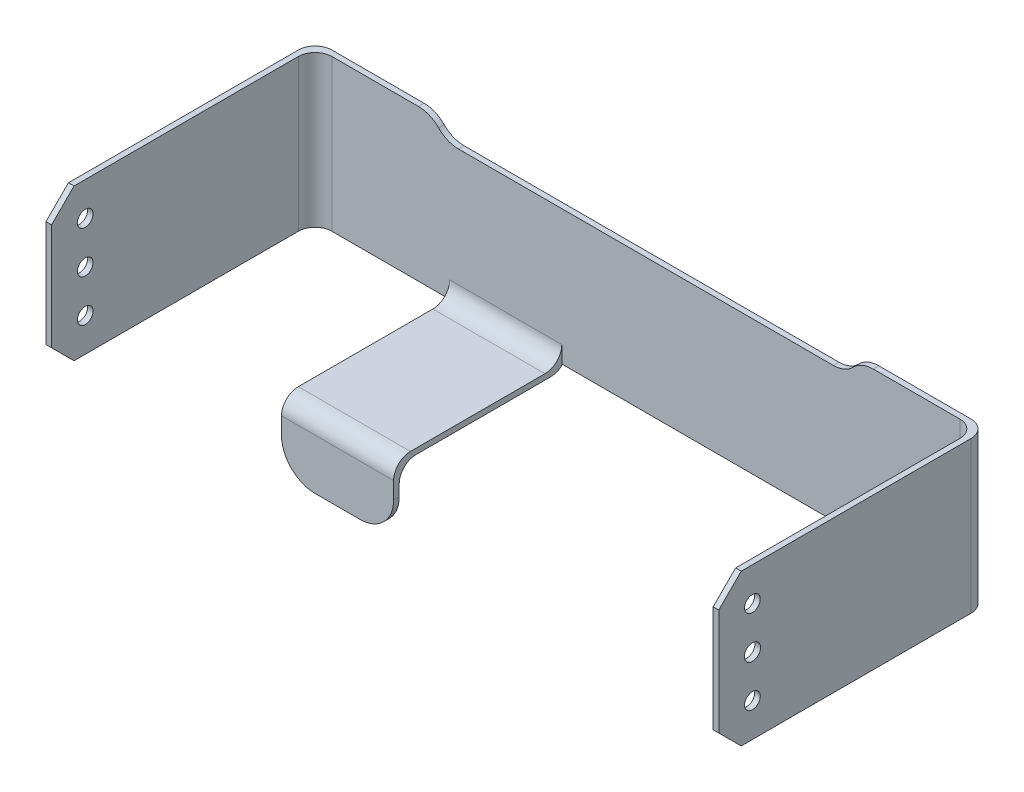
SolidWorks part; units mm, degrees
ref_plane "Front Plane" through (0, 0, 0) normal (0, 0, 1) x (1, 0, 0)
ref_plane "Top Plane" through (0, 0, 0) normal (0, 1, 0) x (1, 0, 0)
ref_plane "Right Plane" through (0, 0, 0) normal (1, 0, 0) x (0, 0, -1)
sketch "Sketch1" plane through (0, 0, 0) normal (0, 0, 1) x (1, 0, 0)
  line L0 (-1120, 0) -> (-60, 0) construction
  line L1 (0, -1000) -> (0, -10.5) construction
  line L9 (60, 0) -> (27292.9876, 0) construction
  line L10 (-38, -13.5) -> (38, -13.5)
  line L11 (-60, -13.5) -> (-60, 13.5)
  line L12 (-60, 13.5) -> (-38, 13.5)
  line L13 (-38, 13.5) -> (-38, 10.5)
  line L14 (-38, 10.5) -> (38, 10.5)
  line L15 (38, 13.5) -> (38, 10.5)
  line L16 (60, 13.5) -> (38, 13.5)
  line L17 (60, -13.5) -> (60, 13.5)
  line L18 (-60, -13.5) -> (-38, -13.5)
  line L22 (60, -13.5) -> (38, -13.5)
  point P13 (0, 10.5)
  point P22 (60, 0)
  dimension "D1" = 38
  dimension "D3" = 13.5
  dimension "D2" = 3
  dimension "D4" = 60
extrude "Boss-Extrude1" add sketch "Sketch1" along normal blind 1
fillet "Fillet1" radius 5 1 edges at (-38, 10.5, 0.5)
fillet "Fillet2" radius 5 1 edges at (-38, 13.5, 0.5)
fillet "Fillet3" radius 5 1 edges at (38, 10.5, 0.5)
fillet "Fillet4" radius 5 1 edges at (38, 13.5, 0.5)
fillet "Fillet5" radius 5 rebuild error yes
fillet "Fillet6" radius 5 rebuild error yes
fillet "Fillet7" radius 5 rebuild error yes
fillet "Fillet8" radius 5 rebuild error yes
sketch "Sketch3" plane through (-60, 0, 0) normal (-1, 0, 0) x (0, 0, 1)
  line L1 (0, 13.5) -> (48, 13.5)
  line L2 (0, 13.5) -> (0, -13.5)
  line L3 (0, -13.5) -> (48, -13.5)
  line L4 (48, 13.5) -> (48, -13.5)
  dimension "D1" = 27
  dimension "D2" = 48
extrude "Boss-Extrude2" add sketch "Sketch3" against normal blind 1
fillet "Fillet9" radius 3 1 edges at (-59, 0, 1)
fillet "Fillet10" radius 3 1 edges at (-60, 0, 0)
sketch "Sketch6" plane through (60, 0, 0) normal (1, 0, 0) x (0, 0, -1)
  line L0 (-4, -13.5) -> (-48, -13.5) construction
  line L1 (0, 13.5) -> (-48, 13.5)
  line L2 (0, 13.5) -> (0, -13.5)
  line L3 (0, -13.5) -> (-48, -13.5)
  line L4 (-48, 13.5) -> (-48, -13.5)
  dimension "D1" = 27
  dimension "D2" = 48
extrude "Boss-Extrude3" add sketch "Sketch6" against normal blind 1
fillet "Fillet11" radius 3 2 edges at (60, 0, 0) (59, 0, 1)
chamfer "Chamfer2" distance 4 angle 45 4 edges at (-59.5, 13.5, 48) (59.5, 13.5, 48) (-59.5, -13.5, 48) (59.5, -13.5, 48)
sketch "Sketch7" plane through (-59, 0, 0) normal (1, 0, 0) x (0, 0, -1)
  line L0 (-52.5702, 0) -> (-1.2913, 0) construction
  line L1 (-42, -16.1386) -> (-42, 18.0257) construction
  line L2 (-48, 9.5) -> (-48, -9.5) construction
  line L3 (-44, 13.5) -> (-3, 13.5) construction
  line L4 (-44, -13.5) -> (-3, -13.5) construction
  circle A0 centre (-42, 0) radius 1.4
  circle A1 centre (-42, 7.5) radius 1.4
  circle A2 centre (-42, -7.5) radius 1.4
  dimension "D2" = 2.8
  dimension "D3" = 2.8
  dimension "D4" = 2.8
  dimension "D1" = 6
  dimension "D5" = 15
  dimension "D6" = 6
  dimension "D7" = 6
extrude "Cut-Extrude1" cut sketch "Sketch7" against normal through all
sketch "Sketch8" plane through (59, 0, 0) normal (-1, 0, 0) x (0, 0, 1)
  line L0 (48, 9.5) -> (48, -9.5) construction
  line L1 (4, 13.5) -> (44, 13.5) construction
  line L2 (44, -13.5) -> (4, -13.5) construction
  circle A0 centre (42, 0) radius 1.445
  circle A1 centre (42, 7.5) radius 1.4
  circle A2 centre (42, -7.5) radius 1.4
  dimension "D1" = 2.8
  dimension "D2" = 2.89
  dimension "D3" = 2.8
  dimension "D4" = 6
  dimension "D5" = 6
  dimension "D6" = 6
  dimension "D7" = 6
  dimension "D8" = 6
  dimension "D9" = 15
  dimension "D10" = 7.5
extrude "Cut-Extrude2" cut sketch "Sketch8" against normal blind 13
sketch "Sketch9" plane through (0, -13.5, 0) normal (0, -1, 0) x (1, 0, 0)
  line L0 (-35, 10.9362) -> (-35, -7.4459) construction
  line L5 (-59, 4) -> (-59, 44) construction
  line L6 (-57, 0) -> (57, 0) construction
  line L7 (-35, 0) -> (-15, 0)
  line L8 (-35, 0) -> (-35, 30)
  line L9 (-35, 30) -> (-15, 30)
  line L10 (-15, 0) -> (-15, 30)
  dimension "D1" = 24
  dimension "D2" = 20
  dimension "D3" = 30
extrude "Boss-Extrude5" add sketch "Sketch9" along normal blind 1
fillet "Fillet13" radius 3 1 edges at (-25, -14.5, 0)
fillet "Fillet14" radius 3 1 edges at (-25, -13.5, 1)
sketch "Sketch10" plane through (0, 0, 30) normal (0, 0, 1) x (1, 0, 0)
  line L1 (-35, -13.5) -> (-15, -13.5)
  line L2 (-35, -13.5) -> (-35, -25.5)
  line L3 (-35, -25.5) -> (-15, -25.5)
  line L4 (-15, -13.5) -> (-15, -25.5)
  dimension "D1" = 12
  dimension "D2" = 20
extrude "Boss-Extrude6" add sketch "Sketch10" along normal blind 1
fillet "Fillet15" radius 3 1 edges at (-25, -13.5, 31)
fillet "Fillet16" radius 3 1 edges at (-25, -14.5, 30)
fillet "Fillet17" radius 6 1 edges at (-35, -25.5, 30.5)
fillet "Fillet18" radius 6 1 edges at (-15, -25.5, 30.5)
